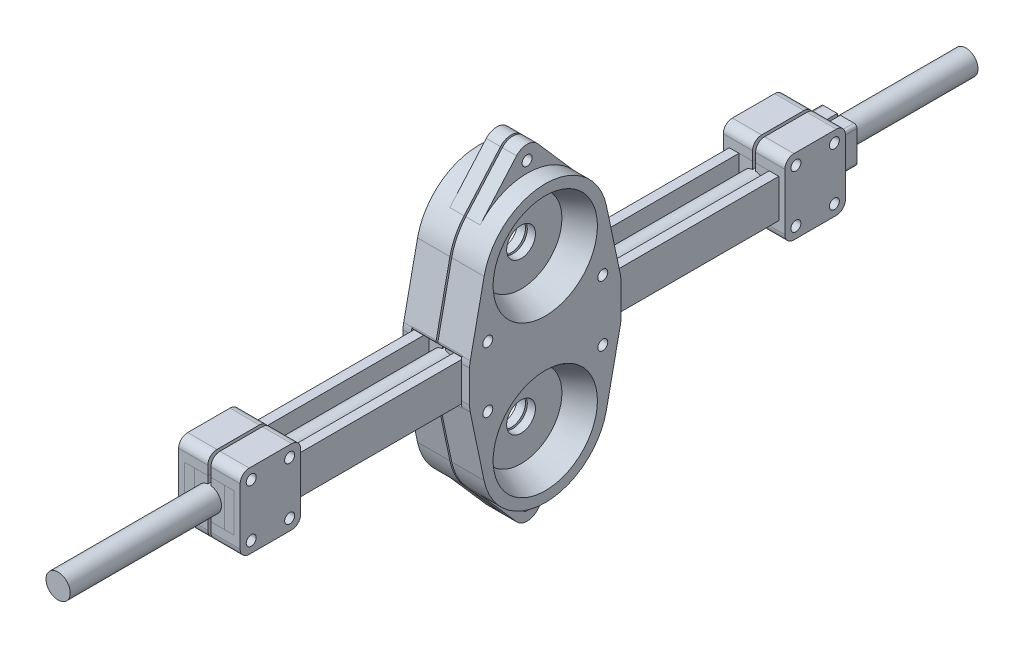
SolidWorks part; units mm, degrees
ref_plane "Front Plane" through (0, 0, 0) normal (0, 0, 1) x (1, 0, 0)
ref_plane "Top Plane" through (0, 0, 0) normal (0, 1, 0) x (1, 0, 0)
ref_plane "Right Plane" through (0, 0, 0) normal (1, 0, 0) x (0, 0, -1)
sketch "Sketch1" plane through (0, 0, 0) normal (0, 0, 1) x (1, 0, 0)
  line L0 (0, 0) -> (0, 67.0118) construction
  line L1 (-6.5875, 0) -> (6.5875, 0) construction
  line L2 (8.175, -6.35) -> (5, -6.35)
  line L3 (-8.175, 6.35) -> (-5, 6.35)
  line L4 (-8.175, 6.35) -> (-8.175, -6.35)
  line L5 (-8.175, -6.35) -> (-5, -6.35)
  line L6 (-5, 6.35) -> (-5, -6.35)
  line L7 (-8.175, 6.35) -> (-5, -6.35) construction
  line L8 (-8.175, -6.35) -> (-5, 6.35) construction
  line L9 (5, 6.35) -> (5, -6.35)
  line L10 (8.175, 6.35) -> (5, 6.35)
  line L11 (8.175, 6.35) -> (8.175, -6.35)
  circle A0 centre (0, 0) radius 4
  dimension "D1" = 8
  dimension "D2" = 12.7
  dimension "D3" = 3.175
  dimension "D4" = 1
extrude "Boss-Extrude1" add sketch "Sketch1" along normal mid plane 200 contours L11 L10 L9 L2 | L6 L3 L4 L5 region at (6.5875, 0, 0) region at (-6.5875, 0, 0)
extrude "Boss-Extrude2" add sketch "Sketch1<3>" along normal mid plane 300 separate body contours A0
sketch "Sketch1<3>" plane through (0, 0, 0) normal (0, 0, 1) x (1, 0, 0) same geometry as "Sketch1"
sketch "Sketch2" plane through (0, 0, 100) normal (0, 0, 1) x (1, 0, 0)
  line L0 (0, 0) -> (0, 8.6431) construction
  line L1 (5, 6.35) -> (5, -6.35)
  line L2 (5, -6.35) -> (0.5, -6.35)
  line L3 (0.5, -6.35) -> (0.5, -3.9686)
  line L4 (0.5, 3.9686) -> (0.5, 6.35)
  line L5 (0.5, 6.35) -> (5, 6.35)
  circle A0 centre (0, 0) radius 4 construction
  circle A1 centre (0, 0) radius 4
  line M3 (5, 6.35) -> (5, -6.35)
  dimension "D1" = 0.5
extrude "Boss-Extrude3" add sketch "Sketch2" against normal blind 20 separate body contours A1 L3 L2 L5 L4 M3 region at (4.8653, 0, 100)
sketch "Sketch4" plane through (0, 0, 100) normal (0, 0, 1) x (1, 0, 0)
  line L0 (0.5, 6.35) -> (8.175, 6.35)
  line L1 (8.175, 6.35) -> (8.175, -6.35)
  line L2 (8.175, -6.35) -> (0.5, -6.35)
  line L3 (8.175, 6.35) -> (8.175, -6.35) construction
  line L4 (0.5, 6.35) -> (0.5, 12.35)
  line L5 (0.5, 12.35) -> (10.175, 12.35)
  line L6 (10.175, 12.35) -> (10.175, -12.35)
  line L7 (10.175, -12.35) -> (0.5, -12.35)
  line L8 (0.5, -12.35) -> (0.5, -6.35)
  dimension "D1" = 6
  dimension "D2" = 2
extrude "Boss-Extrude4" add sketch "Sketch4" against normal up to surface (20 mm away) separate body up to face at (2.5833, 0, 80)
sketch "Sketch5" plane through (0.5, 0, 0) normal (-1, 0, 0) x (0, 0, 1)
  line L0 (80, 11.0312) -> (100, 6.35) construction
  line L5 (80, 6.35) -> (80, 12.35) construction
  line L6 (96.35, 8.6906) -> (83.65, 8.6906) construction
  circle A0 centre (96.35, 8.6906) radius 1.65
  circle A1 centre (83.65, 8.6906) radius 1.65
  point P8 (90, 8.6906)
  dimension "D1" = 3.3
  dimension "D2" = 2
extrude "Cut-Extrude1" cut sketch "Sketch5" against normal through all
mirror "Mirror1" about plane through (0, 0, 0) normal (0, 1, 0) of "Cut-Extrude1"
fillet "Fillet1" radius 3 4 edges at (5.3375, -12.35, 80) (5.3375, -12.35, 100) (5.3375, 12.35, 80) (5.3375, 12.35, 100)
mirror "Mirror2" about plane through (0, 0, 0) normal (1, 0, 0) of bodies 107 110
mirror "Mirror5" about plane through (0, 0, 0) normal (0, 0, 1) of bodies 110 112 107 111
extrude "Boss-Extrude5" add sketch "Sketch2<3>" along normal mid plane 45 from surface separate body contours A1 L3 L2 L5 L4 M3 region at (4.8653, 0, 100) starting at plane "Front Plane"
sketch "Sketch2<3>" plane through (0, 0, 100) normal (0, 0, 1) x (1, 0, 0) same geometry as "Sketch2"
mirror "Mirror4" about plane through (0, 0, 0) normal (1, 0, 0) of bodies 113
sketch "Sketch6" plane through (0, 0, 0) normal (1, 0, 0) x (0, 0, -1)
  line L0 (0, 25) -> (0, -25) construction
  line L2 (-20.2122, 29.2296) -> (-25, 6.35)
  line L3 (-100, 6.35) -> (100, 6.35) construction
  line L4 (20.2122, 29.2296) -> (25, 6.35)
  line L5 (-25, 6.35) -> (25, 6.35)
  line L6 (0, 0) -> (23.5352, 0) construction
  line L7 (-20.2122, -29.2296) -> (-25, -6.35)
  line L8 (20.2122, -29.2296) -> (25, -6.35)
  line L9 (-25, -6.35) -> (25, -6.35)
  line L10 (-25, -6.35) -> (-25, 6.35)
  line L11 (25, 6.35) -> (25, -6.35)
  line L12 (-3.4998, 52.3617) -> (-15.5419, 38.5967)
  line L13 (3.4998, 52.3617) -> (15.5419, 38.5967)
  line L14 (0, 49.3) -> (0, 25) construction
  line L15 (-3.4998, -52.3617) -> (-15.5419, -38.5967)
  line L16 (3.4998, -52.3617) -> (15.5419, -38.5967)
  circle A0 centre (0, 25) radius 4.7625
  circle A1 centre (0, -25) radius 4.7625
  circle A2 centre (0, 25) radius 13.5
  circle A3 centre (0, -25) radius 13.5
  circle A4 centre (0, 25) radius 20.65 construction
  arc A5 (-20.2122, 29.2296) -> (20.2122, 29.2296) centre (0, 25) cw
  arc A6 (-20.2122, -29.2296) -> (20.2122, -29.2296) centre (0, -25) ccw
  circle A7 centre (0, 49.3) radius 1.65
  arc A8 (3.4998, 52.3617) -> (-3.4998, 52.3617) centre (0, 49.3) ccw
  circle A9 centre (0, -49.3) radius 1.65
  arc A10 (3.4998, -52.3617) -> (-3.4998, -52.3617) centre (0, -49.3) cw
  point P22 (0, 50.0406)
  point P24 (0, 6.35)
  dimension "D1" = 9.525
  dimension "D3" = 27
  dimension "D5" = 2
  dimension "D6" = 3.3
  dimension "D7" = 3
  dimension "D8" = 2
  dimension "D2" = 50
  dimension "D4" = 50
extrude "Boss-Extrude6" add sketch "Sketch6" against normal mid plane 6 separate body contours A2 A0 | A3 A1 region at (0, 25, 13.1182) region at (0, -25, 13.1182)
extrude "Boss-Extrude7" add sketch "Sketch6<3>" along normal mid plane 22 contours A5 L2 L5 L4 A2 | L7 A6 L8 L9 A3 | L11 L5 L10 L9 region at (0, 33.9302, 17.9113) region at (0, 0, 0) region at (0, -6.986, 0)
sketch "Sketch6<3>" plane through (0, 0, 0) normal (1, 0, 0) x (0, 0, -1) same geometry as "Sketch6"
extrude "Cut-Extrude2" cut sketch "Sketch6<4>" against normal mid plane 16.5 contours L11 L5 L10 L9 region at (0, 0, 0)
sketch "Sketch6<4>" plane through (0, 0, 0) normal (1, 0, 0) x (0, 0, -1) same geometry as "Sketch6"
draft "Draft1" type of draft neutral plane draft angle 25 faces to draft 2 face at (3, 25, -13.5) face at (3, -25, -13.5) neutral plane through (3, 0, 0) neutral plane normal (1, 0, 0) parameters "D1"=25
draft "Draft2" type of draft neutral plane draft angle 25 faces to draft 2 face at (-11, 25, -13.5) face at (-11, -25, -13.5) neutral plane through (-3, 0, 0) neutral plane normal (-1, 0, 0) parameters "D1"=25
sketch "Sketch7" plane through (11, 0, 0) normal (1, 0, 0) x (0, 0, -1)
  line L1 (-19, -10) -> (19, -10) construction
  line L2 (-19, -10) -> (-19, 10) construction
  line L3 (-19, 10) -> (19, 10) construction
  line L4 (19, -10) -> (19, 10) construction
  line L5 (-19, -10) -> (19, 10) construction
  line L6 (-19, 10) -> (19, -10) construction
  line L10 (-100, 6.35) -> (100, 6.35) construction
  circle A0 centre (-19, 10) radius 1.65
  circle A1 centre (19, 10) radius 1.65
  circle A2 centre (-19, -10) radius 1.65
  circle A3 centre (19, -10) radius 1.65
  point P0 (0, 0)
  point P12 (20.8786, 10)
  point P13 (-19.3111, -10)
  dimension "D1" = 3.3
  dimension "D2" = 2
  dimension "D3" = 38
extrude "Cut-Extrude3" cut sketch "Sketch7" against normal through all
extrude "Boss-Extrude9" add sketch "Sketch6<5>" along normal mid plane 10 contours L13 A8 L12 A5 A7 | A10 L16 A6 L15 A9 region at (0, 45.2509, 9.2599) region at (0, -45.9967, 0)
sketch "Sketch6<5>" plane through (0, 0, 0) normal (1, 0, 0) x (0, 0, -1) same geometry as "Sketch6"
fillet "Fillet2" radius 1 4 edges at (0, 6.35, 25) (0, -6.35, 25) (0, -6.35, -25) (0, 6.35, -25) tangent propagation no
fillet "Fillet3" radius 10 8 edges at (9.625, -6.35, 25) (9.625, 6.35, 25) (9.625, 6.35, -25) (9.625, -6.35, -25) (-9.625, -6.35, -25) (-9.625, 6.35, -25) (-9.625, -6.35, 25) (-9.625, 6.35, 25)
sketch "Sketch8" plane through (0, 0, 0) normal (1, 0, 0) x (0, 0, -1)
  line L1 (-64.7265, 73.8253) -> (42.9221, 73.8253)
  line L2 (-64.7265, 73.8253) -> (-64.7265, -72.7768)
  line L3 (-64.7265, -72.7768) -> (42.9221, -72.7768)
  line L4 (42.9221, 73.8253) -> (42.9221, -72.7768)
extrude "Cut-Extrude4" cut sketch "Sketch8" against normal mid plane 0.6
sketch "Sketch9" plane through (0, 0, -100) normal (0, 0, -1) x (-1, 0, 0)
  line L0 (-0.5, 6) -> (-0.5, -6)
  line L1 (-6, -6) -> (6, -6)
  line L2 (-6, -6) -> (-6, 6)
  line L3 (-6, 6) -> (6, 6)
  line L4 (6, -6) -> (6, 6)
  line L5 (-6, -6) -> (6, 6) construction
  line L6 (-6, 6) -> (6, -6) construction
  line L7 (-0.5, 3.9686) -> (-0.5, 6.35) construction
  line L8 (0.5, 6) -> (0.5, -6)
  line L9 (0.5, 3.9686) -> (0.5, 6.35) construction
  circle A0 centre (0, 0) radius 4 construction
  circle A1 centre (0, 0) radius 4
  point P0 (0, 0)
  arc M5 (-0.5, -3.9686) -> (-0.5, 3.9686) centre (0, 0) cw
  line M6 (-0.5, 3.9686) -> (-0.5, 6.35)
  line M8 (-5, 6.35) -> (-5, -6.35)
  line M10 (-0.5, -6.35) -> (-0.5, -3.9686)
  dimension "D1" = 12
extrude "Boss-Extrude10" add sketch "Sketch9" along normal blind 8 contours L3 L1 M8 M10 M5 M6 | L3 L2 L1 M8 | A1 L8 L1 L4 L3 region at (0.6282, 4.9843, -100) region at (-3.25, 5.868, -100) region at (5.5, 0, -100)
fillet "Fillet4" radius 1 2 edges at (6, -6, -104) (6, 6, -104)
fillet "Fillet5" radius 1 2 edges at (-6, -6, -104) (-6, 6, -104)
